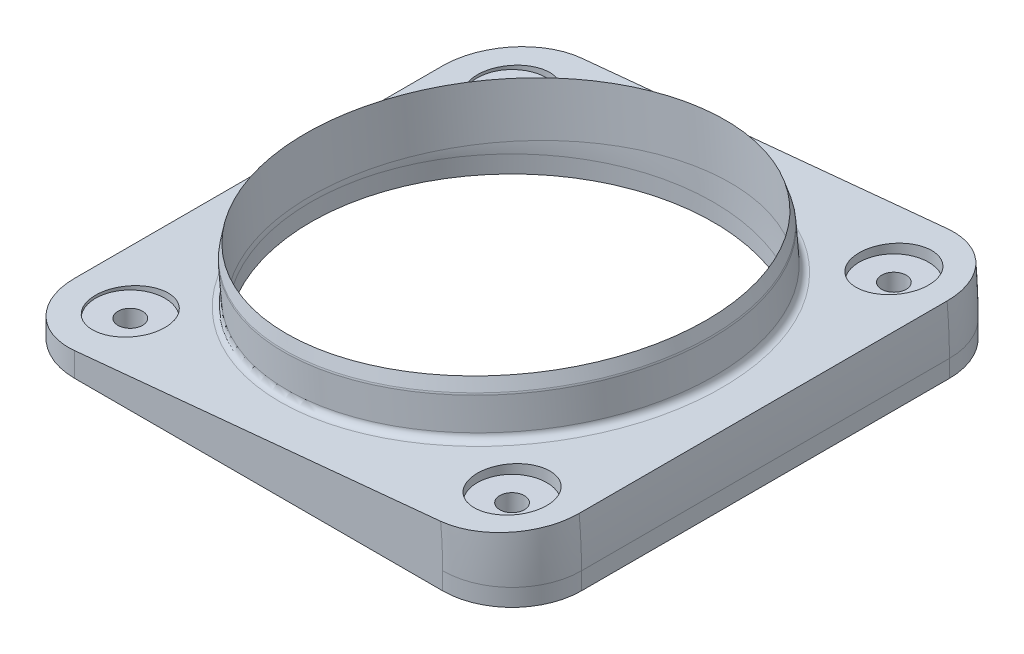
SolidWorks part; units mm, degrees
material "ABS"
ref_plane "Front Plane" through (0, 0, 0) normal (0, 0, 1) x (1, 0, 0)
ref_plane "Top Plane" through (0, 0, 0) normal (0, 1, 0) x (1, 0, 0)
ref_plane "Right Plane" through (0, 0, 0) normal (1, 0, 0) x (0, 0, -1)
sketch "Sketch1" plane through (0, 0, 0) normal (0, 1, 0) x (1, 0, 0)
  line L1 (46.355, -46.355) -> (-46.355, -46.355)
  line L2 (46.355, -46.355) -> (46.355, 46.355)
  line L3 (46.355, 46.355) -> (-46.355, 46.355)
  line L4 (-46.355, -46.355) -> (-46.355, 46.355)
  line L5 (46.355, -46.355) -> (-46.355, 46.355) construction
  line L6 (46.355, 46.355) -> (-46.355, -46.355) construction
  circle A0 centre (0, 0) radius 36.83
  point P0 (0, 0)
  dimension "D1" = 73.66
  dimension "D3" = 92.71
extrude "Boss-Extrude1" add sketch "Sketch1" against normal blind 3.175
revolve "Revolve2" add sketch "Sketch1<2>" angle 5.5 about L4 reverse direction yes
sketch "Sketch1<2>" plane through (0, 0, 0) normal (0, 1, 0) x (1, 0, 0) same geometry as "Sketch1"
sketch "Sketch2" plane through (0, -3.175, 0) normal (0, -1, 0) x (-1, 0, 0)
  line L1 (34.925, -34.925) -> (-34.925, -34.925) construction
  line L2 (34.925, -34.925) -> (34.925, 34.925) construction
  line L3 (34.925, 34.925) -> (-34.925, 34.925) construction
  line L4 (-34.925, -34.925) -> (-34.925, 34.925) construction
  line L5 (34.925, -34.925) -> (-34.925, 34.925) construction
  line L6 (34.925, 34.925) -> (-34.925, -34.925) construction
  circle A0 centre (-34.925, 34.925) radius 2.25
  point P0 (0, 0)
  dimension "D2" = 4.5
  dimension "D1" = 69.85
extrude "Cut-Extrude1" cut sketch "Sketch2" against normal through all
pattern_circular "CirPattern1" count 4 over 360 about axis through (0, -3.175, 0) along (0, 1, 0) of "Cut-Extrude1"
fillet "Fillet1" radius 12.7 6 edges at (-46.355, -1.5875, -46.355) (-46.355, -1.5875, 46.355) (46.355, -1.5875, 46.355) (46.355, -1.5875, -46.355) (46.2482, 4.4481, 46.355) (46.2482, 4.4481, -46.355)
sketch "Sketch4" plane through (0, 0, 0) normal (0, 0, 1) x (1, 0, 0)
  line L1 (-36.8739, 0.9129) -> (-37.7868, 10.3941)
  line L3 (96.0582, -995.3757) -> (-4696.2294, 48774.4342) construction
  line L4 (-37.7868, 10.3941) -> (-38.1917, 7.9743)
  line L5 (-38.1917, 7.9743) -> (-37.5059, 0.8521)
  line L6 (-37.5059, 0.8521) -> (-36.8739, 0.9129)
  line L7 (-36.8739, 0.9129) -> (36.447, 7.9729) construction
  point P10 (-0.2134, 4.4429)
  dimension "D1" = 9.525
  dimension "D2" = 0.635
  dimension "D3" = 15
revolve "Revolve1" add sketch "Sketch4" angle 360 about L3
fillet "Fillet2" radius 1.27 2 edges at (36.3933, 15.156, 0) (37.0791, 8.0338, 0)
ref_plane "Plane1" through (0, 0, 0) normal (0, -1, 0) x (-1, 0, 0)
sketch "Sketch6" plane through (0, 0, 0) normal (0, -1, 0) x (-1, 0, 0)
  circle A0 centre (34.925, -34.925) radius 6.35
  circle A1 centre (34.925, 34.925) radius 6.35
  circle A2 centre (34.925, 34.925) radius 2.25 construction
  circle A3 centre (34.925, -34.925) radius 2.25 construction
  dimension "D1" = 12.7
extrude "Cut-Extrude2" cut sketch "Sketch6" against normal through all
ref_plane "Plane2" through (0, 5.715, 0) normal (0, -1, 0) x (-1, 0, 0)
sketch "Sketch7" plane through (0, 5.715, 0) normal (0, -1, 0) x (-1, 0, 0)
  circle A0 centre (-34.925, 34.925) radius 6.35
  circle A1 centre (-34.925, -34.925) radius 6.35
  circle A2 centre (-34.925, -34.925) radius 2.25 construction
  circle A3 centre (-34.925, 34.925) radius 2.25 construction
  dimension "D1" = 12.7
extrude "Cut-Extrude3" cut sketch "Sketch7" against normal through all
